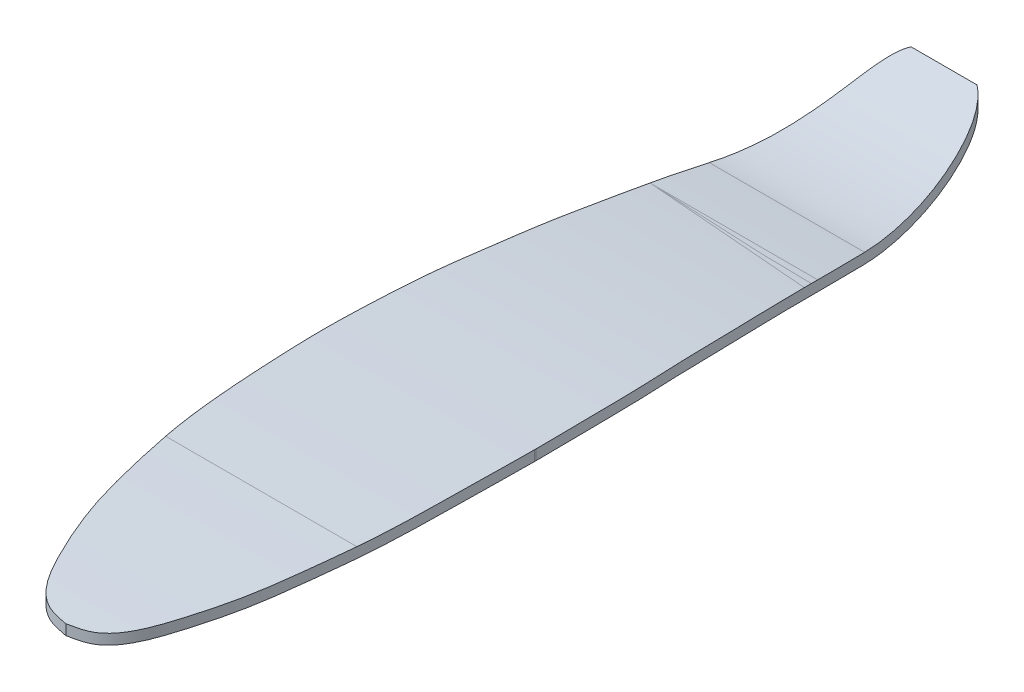
SolidWorks part; units mm, degrees
ref_plane "Front Plane" through (0, 0, 0) normal (0, 0, 1) x (1, 0, 0)
ref_plane "Top Plane" through (0, 0, 0) normal (0, 1, 0) x (1, 0, 0)
ref_plane "Right Plane" through (0, 0, 0) normal (1, 0, 0) x (0, 0, -1)
sketch "Sketch4" plane through (0, 0, 0) normal (1, 0, 0) x (0, 0, -1)
  line L0 (0, 0) -> (700, 0) construction
  line L1 (350, -2957.4869) -> (0, 0) construction
  line L2 (0, 0) -> (-1.1752, 9.9307)
  line L3 (350, -2957.4869) -> (700, 0) construction
  line L4 (700, 0) -> (860, 0) construction
  line L5 (860, 0) -> (860, 45) construction
  line L6 (853.8205, 52.8622) -> (860, 45)
  arc A0 (700, 0) -> (0, 0) centre (350, -2957.4869) ccw
  arc A1 (701.1752, 9.9307) -> (-1.1752, 9.9307) centre (350, -2957.4869) ccw
  arc A4 (700, 0) -> (860, 45) centre (725.5669, 216.0397) ccw
  arc A5 (701.1752, 9.9307) -> (853.8205, 52.8622) centre (725.5669, 216.0397) ccw
  dimension "D1" = 5956.25
  dimension "D2" = 700
  dimension "D3" = 10
  dimension "D4" = 160
  dimension "D5" = 45
  dimension "D6" = 10
extrude "Boss-Extrude1" add sketch "Sketch4" along normal mid plane 204
curve "Curve4"
  spline degree 3 poles (0, 0, 0) (-6.9497, 0, -1.1765) (-35.0703, 0, -5.9371) (-58.3482, 0, -53.1428) (-77.0375, 0, -103.6376) (-87.1805, 0, -154.8922) (-95.8463, 0, -204.7039) (-99.2669, 0, -254.967) (-101.0605, 0, -304.9801) (-102.4875, 0, -355.0029) (-100.9888, 0, -405.0082) (-99.5542, 0, -455.0743) (-94.7768, 0, -504.9834) (-91.3326, 0, -555.0616) (-85.8743, 0, -604.9784) (-81.1634, 0, -655.091) (-75.435, 0, -705.0027) (-66.9819, 0, -755.6965) (-58.1589, 0, -804.9148) (-41.957, 0, -858.7275) (-10.8462, 0, -859.6711) (0, 0, -860) knots 0 0 0 0 0.022198 0.089822 0.147044 0.20217 0.256694 0.310706 0.364588 0.418438 0.472288 0.52617 0.580182 0.634193 0.688301 0.742408 0.796634 0.851158 0.906063 0.967251 1 1 1 1
curve "Curve5"
  spline degree 3 poles (0, 0, 0) (6.9497, 0, -1.1765) (35.0703, 0, -5.9371) (58.3482, 0, -53.1428) (77.0375, 0, -103.6376) (87.1805, 0, -154.8922) (95.8463, 0, -204.7039) (99.2669, 0, -254.967) (101.0605, 0, -304.9801) (102.4875, 0, -355.0029) (100.9888, 0, -405.0082) (99.5542, 0, -455.0743) (94.7768, 0, -504.9834) (91.3326, 0, -555.0616) (85.8743, 0, -604.9784) (81.1634, 0, -655.091) (75.435, 0, -705.0027) (66.9819, 0, -755.6965) (58.1589, 0, -804.9148) (41.957, 0, -858.7275) (10.8462, 0, -859.6711) (0, 0, -860) knots 0 0 0 0 0.022198 0.089822 0.147044 0.20217 0.256694 0.310706 0.364588 0.418438 0.472288 0.52617 0.580182 0.634193 0.688301 0.742408 0.796634 0.851158 0.906063 0.967251 1 1 1 1
sketch "Sketch9" plane through (0, 0, 0) normal (0, 1, 0) x (1, 0, 0)
  spline S0 degree 3 poles (1282.9582, -2705.0091) (-288.5669, 190.9166) (-7.7589, -80.917) (58.3482, 53.1428) (77.0375, 103.6376) (87.1805, 154.8922) (95.8463, 204.7039) (99.2669, 254.967) (101.0605, 304.9801) (102.4875, 355.0029) (100.9888, 405.0082) (99.5542, 455.0743) (94.7768, 504.9834) (91.3326, 555.0616) (85.8743, 604.9784) (81.1634, 655.091) (75.435, 705.0027) (66.9819, 755.6965) (58.1589, 804.9148) (10.9408, 961.7437) (-370.0506, 561.6004) (1388.8093, 3511.7646) knots -0.270547 -0.270547 -0.270547 -0.270547 0.022198 0.089822 0.147044 0.20217 0.256694 0.310706 0.364588 0.418438 0.472288 0.52617 0.580182 0.634193 0.688301 0.742408 0.796634 0.851158 0.906063 0.967251 1.284935 1.284935 1.284935 1.284935 only from (0, 0) to (0, 860) construction
  spline S1 degree 3 poles (0, 0) (6.9497, 1.1765) (35.0703, 5.9371) (58.3482, 53.1428) (77.0375, 103.6376) (87.1805, 154.8922) (95.8463, 204.7039) (99.2669, 254.967) (101.0605, 304.9801) (102.4875, 355.0029) (100.9888, 405.0082) (99.5542, 455.0743) (94.7768, 504.9834) (91.3326, 555.0616) (85.8743, 604.9784) (81.1634, 655.091) (75.435, 705.0027) (66.9819, 755.6965) (58.1589, 804.9148) (41.957, 858.7275) (10.8462, 859.6711) (0, 860) knots 0 0 0 0 0.022198 0.089822 0.147044 0.20217 0.256694 0.310706 0.364588 0.418438 0.472288 0.52617 0.580182 0.634193 0.688301 0.742408 0.796634 0.851158 0.906063 0.967251 1 1 1 1
  spline S2 degree 3 poles (-1282.9582, -2705.0091) (288.5669, 190.9166) (7.7589, -80.917) (-58.3482, 53.1428) (-77.0375, 103.6376) (-87.1805, 154.8922) (-95.8463, 204.7039) (-99.2669, 254.967) (-101.0605, 304.9801) (-102.4875, 355.0029) (-100.9888, 405.0082) (-99.5542, 455.0743) (-94.7768, 504.9834) (-91.3326, 555.0616) (-85.8743, 604.9784) (-81.1634, 655.091) (-75.435, 705.0027) (-66.9819, 755.6965) (-58.1589, 804.9148) (-10.9408, 961.7437) (370.0506, 561.6004) (-1388.8093, 3511.7646) knots -0.270547 -0.270547 -0.270547 -0.270547 0.022198 0.089822 0.147044 0.20217 0.256694 0.310706 0.364588 0.418438 0.472288 0.52617 0.580182 0.634193 0.688301 0.742408 0.796634 0.851158 0.906063 0.967251 1.284935 1.284935 1.284935 1.284935 only from (0, 0) to (0, 860) construction
  spline S3 degree 3 poles (0, 0) (-6.9497, 1.1765) (-35.0703, 5.9371) (-58.3482, 53.1428) (-77.0375, 103.6376) (-87.1805, 154.8922) (-95.8463, 204.7039) (-99.2669, 254.967) (-101.0605, 304.9801) (-102.4875, 355.0029) (-100.9888, 405.0082) (-99.5542, 455.0743) (-94.7768, 504.9834) (-91.3326, 555.0616) (-85.8743, 604.9784) (-81.1634, 655.091) (-75.435, 705.0027) (-66.9819, 755.6965) (-58.1589, 804.9148) (-41.957, 858.7275) (-10.8462, 859.6711) (0, 860) knots 0 0 0 0 0.022198 0.089822 0.147044 0.20217 0.256694 0.310706 0.364588 0.418438 0.472288 0.52617 0.580182 0.634193 0.688301 0.742408 0.796634 0.851158 0.906063 0.967251 1 1 1 1
extrude "Cut-Extrude1" cut sketch "Sketch9" against normal blind 100 and the other way blind 100 flip side to cut
ref_plane "Plane1" through (0, 100, 0) normal (0, 1, 0) x (1, 0, 0)
sketch "Sketch11" plane through (0, 100, 0) normal (0, 1, 0) x (1, 0, 0)
  line L1 (-92.9742, 190) -> (92.9742, 190)
  line L2 (-81.5168, 650) -> (81.5168, 650)
  spline S0 degree 3 poles (809.203, -1824.4086) (-238.0513, 143.5072) (-2.4292, -70.1088) (58.3482, 53.1428) (77.0375, 103.6376) (87.1805, 154.8922) (95.8463, 204.7039) (99.2669, 254.967) (101.0605, 304.9801) (102.4875, 355.0029) (100.9888, 405.0082) (99.5542, 455.0743) (94.7768, 504.9834) (91.3326, 555.0616) (85.8743, 604.9784) (81.1634, 655.091) (75.435, 705.0027) (66.9819, 755.6965) (58.1589, 804.9148) (14.7523, 949.0846) (-302.5322, 630.9729) (879.8794, 2651.1271) knots -0.236879 -0.236879 -0.236879 -0.236879 0.022198 0.089822 0.147044 0.20217 0.256694 0.310706 0.364588 0.418438 0.472288 0.52617 0.580182 0.634193 0.688301 0.742408 0.796634 0.851158 0.906063 0.967251 1.249921 1.249921 1.249921 1.249921 only from (0, 0) to (0, 860) construction
  spline S1 degree 3 poles (-809.203, -1824.4086) (238.0513, 143.5072) (2.4292, -70.1088) (-58.3482, 53.1428) (-77.0375, 103.6376) (-87.1805, 154.8922) (-95.8463, 204.7039) (-99.2669, 254.967) (-101.0605, 304.9801) (-102.4875, 355.0029) (-100.9888, 405.0082) (-99.5542, 455.0743) (-94.7768, 504.9834) (-91.3326, 555.0616) (-85.8743, 604.9784) (-81.1634, 655.091) (-75.435, 705.0027) (-66.9819, 755.6965) (-58.1589, 804.9148) (-14.7523, 949.0846) (302.5322, 630.9729) (-879.8794, 2651.1271) knots -0.236879 -0.236879 -0.236879 -0.236879 0.022198 0.089822 0.147044 0.20217 0.256694 0.310706 0.364588 0.418438 0.472288 0.52617 0.580182 0.634193 0.688301 0.742408 0.796634 0.851158 0.906063 0.967251 1.249921 1.249921 1.249921 1.249921 only from (0, 0) to (0, 860) construction
  spline S2 degree 3 poles (92.9742, 190) (93.7159, 194.9913) (96.6508, 216.5252) (99.2669, 254.967) (101.0605, 304.9801) (102.4875, 355.0029) (100.9888, 405.0082) (99.5542, 455.0743) (94.7768, 504.9834) (91.3326, 555.0616) (86.0566, 603.3111) (83.0516, 635.0195) (81.5168, 650) knots 0.240369 0.240369 0.240369 0.240369 0.256694 0.310706 0.364588 0.418438 0.472288 0.52617 0.580182 0.634193 0.688301 0.73699 0.73699 0.73699 0.73699
  spline S3 degree 3 poles (-92.9742, 190) (-93.7159, 194.9913) (-96.6508, 216.5252) (-99.2669, 254.967) (-101.0605, 304.9801) (-102.4875, 355.0029) (-100.9888, 405.0082) (-99.5542, 455.0743) (-94.7768, 504.9834) (-91.3326, 555.0616) (-86.0566, 603.3111) (-83.0516, 635.0195) (-81.5168, 650) knots 0.240369 0.240369 0.240369 0.240369 0.256694 0.310706 0.364588 0.418438 0.472288 0.52617 0.580182 0.634193 0.688301 0.73699 0.73699 0.73699 0.73699
  point P0 (0, 190)
  point P1 (0, 650)
curve "Curve6"
  spline degree 3 poles (0, 100, 0) (-6.9497, 100, -1.1765) (-35.0703, 100, -5.9371) (-58.3482, 100, -53.1428) (-77.0375, 100, -103.6376) (-87.1805, 100, -154.8922) (-95.8463, 100, -204.7039) (-99.2669, 100, -254.967) (-101.0605, 100, -304.9801) (-102.4875, 100, -355.0029) (-100.9888, 100, -405.0082) (-99.5542, 100, -455.0743) (-94.7768, 100, -504.9834) (-91.3326, 100, -555.0616) (-85.8743, 100, -604.9784) (-81.1634, 100, -655.091) (-75.435, 100, -705.0027) (-66.9819, 100, -755.6965) (-58.1589, 100, -804.9148) (-41.957, 100, -858.7275) (-10.8462, 100, -859.6711) (0, 100, -860) knots 0 0 0 0 0.022198 0.089822 0.147044 0.20217 0.256694 0.310706 0.364588 0.418438 0.472288 0.52617 0.580182 0.634193 0.688301 0.742408 0.796634 0.851158 0.906063 0.967251 1 1 1 1
curve "Curve7"
  spline degree 3 poles (0, 100, 0) (6.9497, 100, -1.1765) (35.0703, 100, -5.9371) (58.3482, 100, -53.1428) (77.0375, 100, -103.6376) (87.1805, 100, -154.8922) (95.8463, 100, -204.7039) (99.2669, 100, -254.967) (101.0605, 100, -304.9801) (102.4875, 100, -355.0029) (100.9888, 100, -405.0082) (99.5542, 100, -455.0743) (94.7768, 100, -504.9834) (91.3326, 100, -555.0616) (85.8743, 100, -604.9784) (81.1634, 100, -655.091) (75.435, 100, -705.0027) (66.9819, 100, -755.6965) (58.1589, 100, -804.9148) (41.957, 100, -858.7275) (10.8462, 100, -859.6711) (0, 100, -860) knots 0 0 0 0 0.022198 0.089822 0.147044 0.20217 0.256694 0.310706 0.364588 0.418438 0.472288 0.52617 0.580182 0.634193 0.688301 0.742408 0.796634 0.851158 0.906063 0.967251 1 1 1 1
wrap "Wrap8" sketch "Sketch11" wrap type scribe source sketch "Sketch11" face at (-3.1381, 23.1579, -327.3608)
